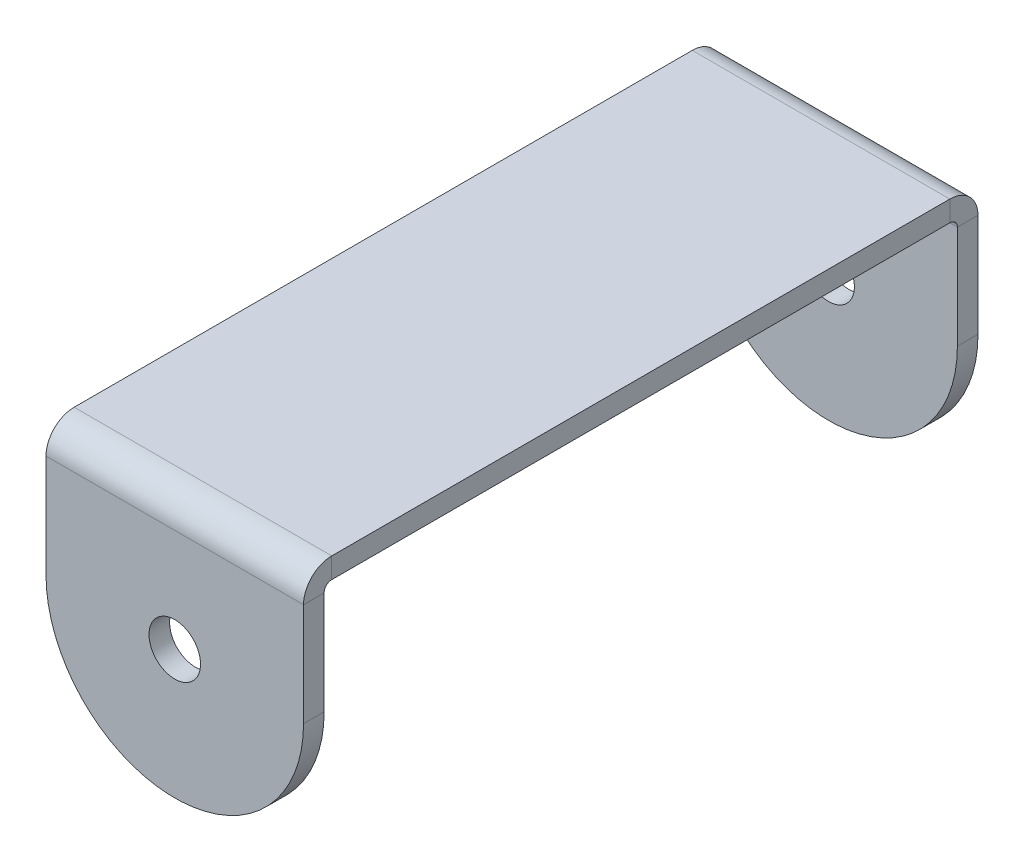
SolidWorks part; units mm, degrees
note: The reader was unsure of these and kept them because the rebuilt part matched: flange length of "Edge-Flange1".
ref_plane "Front Plane" through (0, 0, 0) normal (0, 0, 1) x (1, 0, 0)
ref_plane "Top Plane" through (0, 0, 0) normal (0, 1, 0) x (1, 0, 0)
ref_plane "Right Plane" through (0, 0, 0) normal (1, 0, 0) x (0, 0, -1)
sketch "Sketch1" plane through (0, 0, 0) normal (0, 1, 0) x (1, 0, 0)
  line L1 (0, 0) -> (25, 0)
  line L2 (0, 0) -> (0, 60)
  line L3 (0, 60) -> (25, 60)
  line L4 (25, 0) -> (25, 60)
  dimension "D1" = 25
  dimension "D2" = 60
base flange "Base-Flange1" sketch "Sketch1" thickness 2 reverse thickness direction no parameters "D1"=0.7366
edge flange "Edge-Flange1" sketch "Sketch10" flange profiles "Sketch10", "Sketch11" flange angle 90 flange length 30 flange position bend outside bend radius 0.7366 thickness 2 relief rectangular parameters "D6"=10, "D8"=1
sketch "Sketch10" plane through (0, -2, 0) normal (0, 0, 1) x (-1, 0, 0)
  line L0 (0, 0) -> (-25, 0) construction
  line L1 (0, 0) -> (-25, 0)
  line L2 (-25, 0) -> (-25, 28)
  line L3 (-25, 28) -> (0, 28)
  line L4 (0, 28) -> (0, 0)
sketch "Sketch11" plane through (0, -2, -60) normal (0, 0, -1) x (1, 0, 0)
  line L0 (25, 0) -> (0, 0) construction
  line L1 (25, 0) -> (0, 0)
  line L2 (0, 0) -> (0, 28)
  line L3 (0, 28) -> (25, 28)
  line L4 (25, 28) -> (25, 0)
bend "EdgeBend1" bend radius 0.7366 bend angle 90 parameters "D5"=1
bend "EdgeBend2" bend radius 0.7366 bend angle 90 parameters "D5"=2
sketch "Sketch12" plane through (0, 0, -62.7366) normal (0, 0, -1) x (-1, 0, 0)
  line L3 (-25, -12.7366) -> (-25, -30)
  line L4 (-25, -2.7366) -> (0, -2.7366) construction
  line L5 (0, -30) -> (0, -12.7366)
  line L6 (0, -30) -> (0, -2.7366) construction
  line L7 (-25, -2.7366) -> (-25, -30) construction
  line L8 (-25, -30) -> (0, -30)
  line L9 (-25, -30) -> (0, -30) construction
  arc A0 (-25, -12.7366) -> (0, -12.7366) centre (-12.5, -12.7366) ccw
  circle A1 centre (-12.5, -12.7366) radius 2.5
  point P3 (-12.5, -2.7366)
  dimension "D2" = 12.5
  dimension "D3" = 5
  dimension "D1" = 10
extrude "Cut-Extrude1" cut sketch "Sketch12" against normal up to surface (65.4732 mm away) normal cut yes up to face at (12.5, -16.3683, 2.7366)
sketch "Bend-Lines1" plane through (0, 0, 0) normal (0, 1, 0) x (1, 0, 0)
sketch "Bounding-Box1" plane through (0, 0, 0) normal (0, 1, 0) x (1, 0, 0)
sheet metal parameters "Sheet-Metal1" thickness 2 parameters "D1"=0.7366
flat pattern "Flat-Pattern1" [suppressed]
sketch "Bend-Lines2" plane through (0, 0, 0) normal (0, 1, 0) x (1, 0, 0)
sketch "Bounding-Box2" [suppressed] plane through (0, 0, 0) normal (0, 1, 0) x (1, 0, 0)
sheet metal parameters "Sheet-Metal2" thickness 2 parameters "D1"=0.7366
flat pattern "Flat-Pattern1" [suppressed]
sketch "Bend-Lines2" plane through (0, 0, 0) normal (0, 1, 0) x (1, 0, 0)
sketch "Bounding-Box2" [suppressed] plane through (0, 0, 0) normal (0, 1, 0) x (1, 0, 0)
bend of the flat pattern "Flatten-<EdgeBend1>1"
bend of the flat pattern "Flatten-<EdgeBend2>1"
sheet metal parameters "Sheet-Metal3" thickness 2 parameters "D1"=0.7366
flat pattern "Flat-Pattern1" [suppressed]
sketch "Bend-Lines2" plane through (0, 0, 0) normal (0, 1, 0) x (1, 0, 0)
sketch "Bounding-Box2" [suppressed] plane through (0, 0, 0) normal (0, 1, 0) x (1, 0, 0)
bend of the flat pattern "Flatten-<EdgeBend1>1"
bend of the flat pattern "Flatten-<EdgeBend2>1"
